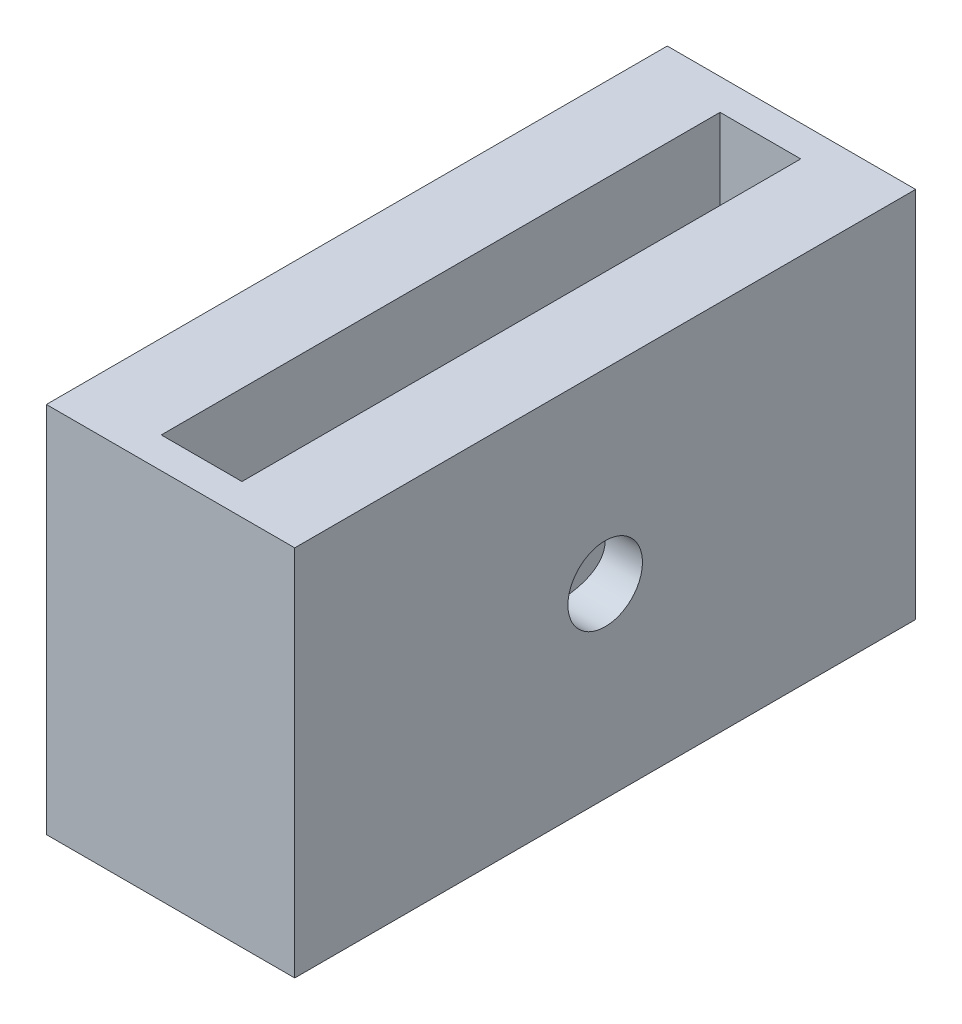
SolidWorks part; units mm, degrees
ref_plane "Front Plane" through (0, 0, 0) normal (0, 0, 1) x (1, 0, 0)
ref_plane "Top Plane" through (0, 0, 0) normal (0, 1, 0) x (1, 0, 0)
ref_plane "Right Plane" through (0, 0, 0) normal (1, 0, 0) x (0, 0, -1)
sketch "Sketch1" plane through (0, 0, 0) normal (0, 0, 1) x (1, 0, 0)
  line L5 (-10, -15) -> (10, -15)
  line L6 (-10, -15) -> (-10, 15)
  line L7 (-10, 15) -> (10, 15)
  line L8 (10, -15) -> (10, 15)
  line L9 (-10, -15) -> (10, 15) construction
  line L10 (-10, 15) -> (10, -15) construction
  point P0 (0, 0)
  dimension "D1" = 20
  dimension "D2" = 30
extrude "Boss-Extrude1" add sketch "Sketch1" along normal blind 50
sketch "Sketch3" plane through (0, 0, 0) normal (0, 0, 1) x (1, 0, 0)
  circle A0 centre (0, 0) radius 7
  point P2 (0, 0)
  point P3 (0, 0)
  dimension "D1" = 14
extrude "Cut-Extrude1" cut sketch "Sketch3" along normal blind 40
sketch "Sketch4" plane through (-10, 0, 0) normal (-1, 0, 0) x (0, 0, 1)
  circle A0 centre (25, 0) radius 3
  point P2 (24.6442, 4.2027)
  dimension "D1" = 25
  dimension "D2" = 6
  dimension "D3" = 0
extrude "Cut-Extrude2" cut sketch "Sketch4" against normal through all
sketch "Sketch5" plane through (0, 15, 0) normal (0, 1, 0) x (1, 0, 0)
  line L1 (-3.25, -47.5) -> (3.25, -47.5)
  line L2 (-3.25, -47.5) -> (-3.25, -2.5)
  line L3 (-3.25, -2.5) -> (3.25, -2.5)
  line L4 (3.25, -47.5) -> (3.25, -2.5)
  line L5 (-3.25, -47.5) -> (3.25, -2.5) construction
  line L6 (-3.25, -2.5) -> (3.25, -47.5) construction
  point P0 (0, -25)
  point P5 (-2.3075, -24.8933)
  dimension "D1" = 25
  dimension "D2" = 45
  dimension "D3" = 0
  dimension "D4" = 6.5
extrude "Cut-Extrude3" cut sketch "Sketch5" against normal through all
